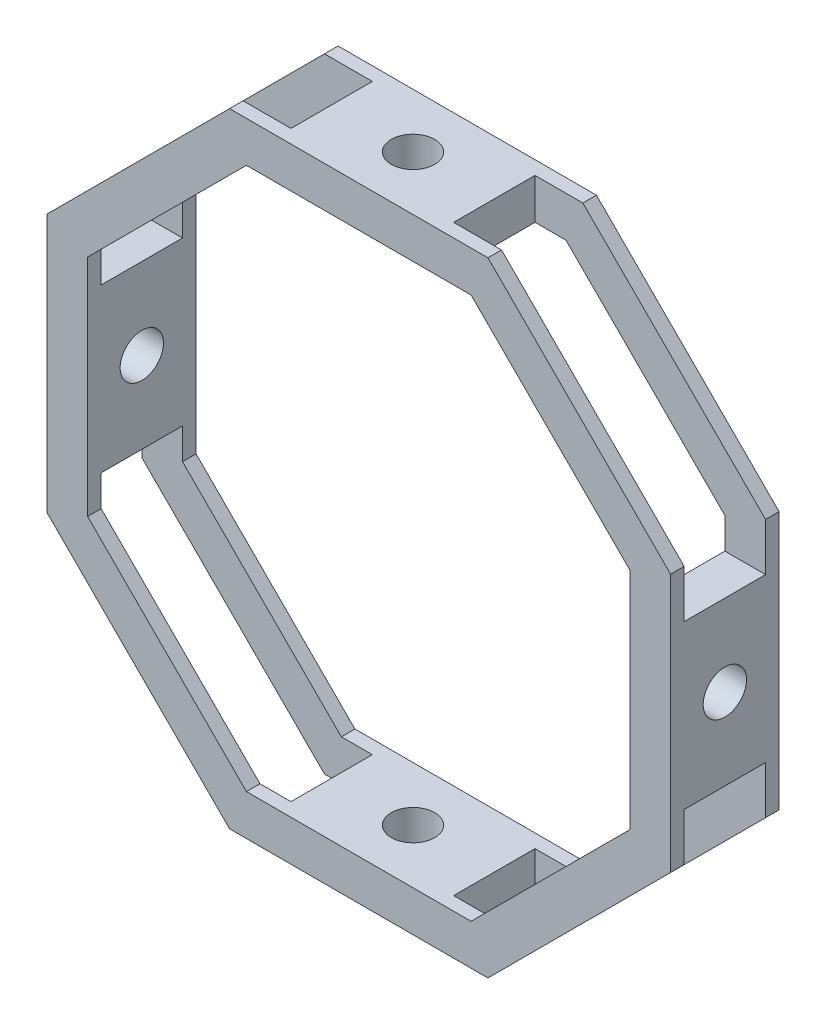
SolidWorks part; units mm, degrees
ref_plane "Plano frontal" through (0, 0, 0) normal (0, 0, 1) x (1, 0, 0)
ref_plane "Plano superior" through (0, 0, 0) normal (0, 1, 0) x (1, 0, 0)
ref_plane "Plano direito" through (0, 0, 0) normal (1, 0, 0) x (0, 0, -1)
sketch "Esboço1" plane through (0, 0, 0) normal (0, 0, 1) x (1, 0, 0)
  line L1 (115, 47.6346) -> (47.6346, 115)
  line L2 (47.6346, 115) -> (-47.6346, 115)
  line L3 (-47.6346, 115) -> (-115, 47.6346)
  line L4 (-115, 47.6346) -> (-115, -47.6346)
  line L5 (-115, -47.6346) -> (-47.6346, -115)
  line L6 (-47.6346, -115) -> (47.6346, -115)
  line L7 (47.6346, -115) -> (115, -47.6346)
  line L8 (115, -47.6346) -> (115, 47.6346)
  line L9 (100, 41.4214) -> (41.4214, 100)
  line L10 (41.4214, 100) -> (-41.4214, 100)
  line L11 (-41.4214, 100) -> (-100, 41.4214)
  line L12 (-100, 41.4214) -> (-100, -41.4214)
  line L13 (-100, -41.4214) -> (-41.4214, -100)
  line L14 (-41.4214, -100) -> (41.4214, -100)
  line L15 (41.4214, -100) -> (100, -41.4214)
  line L16 (100, -41.4214) -> (100, 41.4214)
  circle A0 centre (0, 0) radius 115 construction
  circle A1 centre (0, 0) radius 100 construction
extrude "Ressalto-extrusão1" add sketch "Esboço1" along normal blind 40
sketch "Esboço2" plane through (115, 0, 0) normal (1, 0, 0) x (0, 0, -1)
  line L0 (-40, -47.6346) -> (-40, 47.6346) construction
  line L1 (0, 0) -> (-40, 0)
  line L2 (0, 0) -> (0, 30)
  line L3 (0, 30) -> (-40, 30)
  line L4 (-40, 0) -> (-40, 30)
  line L5 (-40, -47.6346) -> (0, -47.6346) construction
  line L6 (0, 0) -> (-40, 0)
  line L7 (0, 0) -> (0, -30)
  line L8 (0, -30) -> (-40, -30)
  line L9 (-40, 0) -> (-40, -30)
  line L10 (0, 47.6346) -> (-5, 47.6346)
  line L11 (0, 47.6346) -> (0, 30)
  line L12 (0, 30) -> (-5, 30)
  line L13 (-5, 47.6346) -> (-5, 30)
  line L14 (-40, 47.6346) -> (-35, 47.6346)
  line L15 (-40, 47.6346) -> (-40, 30)
  line L16 (-40, 30) -> (-35, 30)
  line L17 (-35, 47.6346) -> (-35, 30)
  line L18 (-5, -30) -> (-35, -30)
  line L19 (-5, -30) -> (-5, -47.6346)
  line L20 (-5, -47.6346) -> (-35, -47.6346)
  line L21 (-35, -30) -> (-35, -47.6346)
  circle A0 centre (-20, 0) radius 8
  line M2 (0, 47.6346) -> (-40, 47.6346)
  line M4 (-40, -47.6346) -> (0, -47.6346)
extrude "Corte-extrusão1" cut sketch "Esboço2" against normal through all both and the other way through all contours L17 L3 L13 M2 | L8 L21 L19 M4 | L6 A0 | L6 A0 region at (115, -3.3953, 20) region at (115, 3.3953, 20) region at (115, 38.8173, 20) region at (115, -38.8173, 20)
sketch "Esboço3" plane through (0, 115, 0) normal (0, 1, 0) x (1, 0, 0)
  line L0 (47.6346, -40) -> (-47.6346, -40) construction
  line L1 (0, 0) -> (30, 0)
  line L2 (0, 0) -> (0, -40)
  line L3 (0, -40) -> (30, -40)
  line L4 (30, 0) -> (30, -40)
  line L5 (47.6346, -40) -> (47.6346, 0) construction
  line L6 (0, 0) -> (-30, 0)
  line L7 (0, 0) -> (0, -40)
  line L8 (0, -40) -> (-30, -40)
  line L9 (-30, 0) -> (-30, -40)
  line L10 (-47.6346, 0) -> (-30, 0)
  line L11 (-47.6346, 0) -> (-47.6346, -5)
  line L12 (-47.6346, -5) -> (-30, -5)
  line L13 (-30, 0) -> (-30, -5)
  line L14 (-47.6346, -40) -> (-30, -40)
  line L15 (-47.6346, -40) -> (-47.6346, -35)
  line L16 (-47.6346, -35) -> (-30, -35)
  line L17 (-30, -40) -> (-30, -35)
  line L18 (30, -35) -> (47.6346, -35)
  line L19 (30, -35) -> (30, -5)
  line L20 (30, -5) -> (47.6346, -5)
  line L21 (47.6346, -35) -> (47.6346, -5)
  circle A0 centre (0, -20) radius 8
  line M2 (-47.6346, 0) -> (-47.6346, -40)
  line M4 (47.6346, -40) -> (47.6346, 0)
extrude "Corte-extrusão2" cut sketch "Esboço3" against normal through all both and the other way through all contours L7 A0 | L7 A0 | L20 L4 L18 M4 | L16 L9 L12 M2 region at (3.3953, 115, 20) region at (-3.3953, 115, 20) region at (38.8173, 115, 20) region at (-38.8173, 115, 20)
sketch "Esboço4" plane through (81.3173, 81.3173, 0) normal (0.7071, 0.7071, 0) x (0, 0, -1)
  line L0 (-35, -47.6346) -> (-5, -47.6346) construction
  line L1 (-35, 47.6346) -> (-5, 47.6346)
  line L2 (-35, 47.6346) -> (-35, -47.6346)
  line L3 (-35, -47.6346) -> (-5, -47.6346)
  line L4 (-5, 47.6346) -> (-5, -47.6346)
extrude "Corte-extrusão3" cut sketch "Esboço4" against normal through all both and the other way through all
sketch "Esboço5" plane through (-81.3173, 81.3173, 0) normal (-0.7071, 0.7071, 0) x (0, 0, 1)
  line L1 (35, 47.6346) -> (5, 47.6346)
  line L2 (35, 47.6346) -> (35, -47.6346)
  line L3 (35, -47.6346) -> (5, -47.6346)
  line L4 (5, 47.6346) -> (5, -47.6346)
extrude "Corte-extrusão4" cut sketch "Esboço5" against normal through all both and the other way through all
